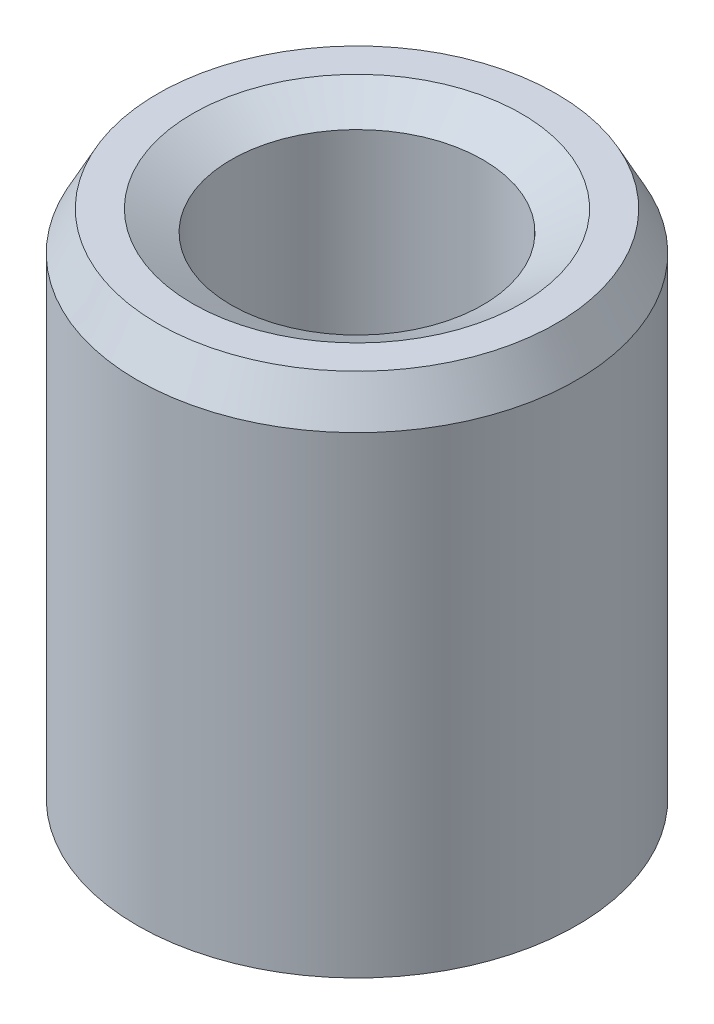
SolidWorks part; units mm, degrees
ref_plane "Front Plane" through (0, 0, 0) normal (0, 0, 1) x (1, 0, 0)
ref_plane "Top Plane" through (0, 0, 0) normal (0, 1, 0) x (1, 0, 0)
ref_plane "Right Plane" through (0, 0, 0) normal (1, 0, 0) x (0, 0, -1)
sketch "Sketch1" plane through (0, 0, 0) normal (0, 1, 0) x (1, 0, 0)
  circle A0 centre (0, 0) radius 17.5
  dimension "SLEEVE_OD" = 35
extrude "Boss-Extrude1" add sketch "Sketch1" along normal blind 42.3252
sketch "Sketch2" plane through (0, 0, 0) normal (0, 1, 0) x (1, 0, 0)
  circle A0 centre (0, 0) radius 10.0231
  dimension "BORE_D" = 20.0462
extrude "Cut-Extrude1" cut sketch "Sketch2" along normal through all
chamfer "Chamfer1" distance 3.0781 angle 27.974 4 edges at (0, 42.3252, 10.0231) (0, 0, 10.0231) (0, 0, 17.5) (0, 42.3252, 17.5) first distance on face at (0, 42.3252, 10.0231) first distance on face at (0, 0, 10.0231) first distance on face at (0, 42.3252, 17.5)
